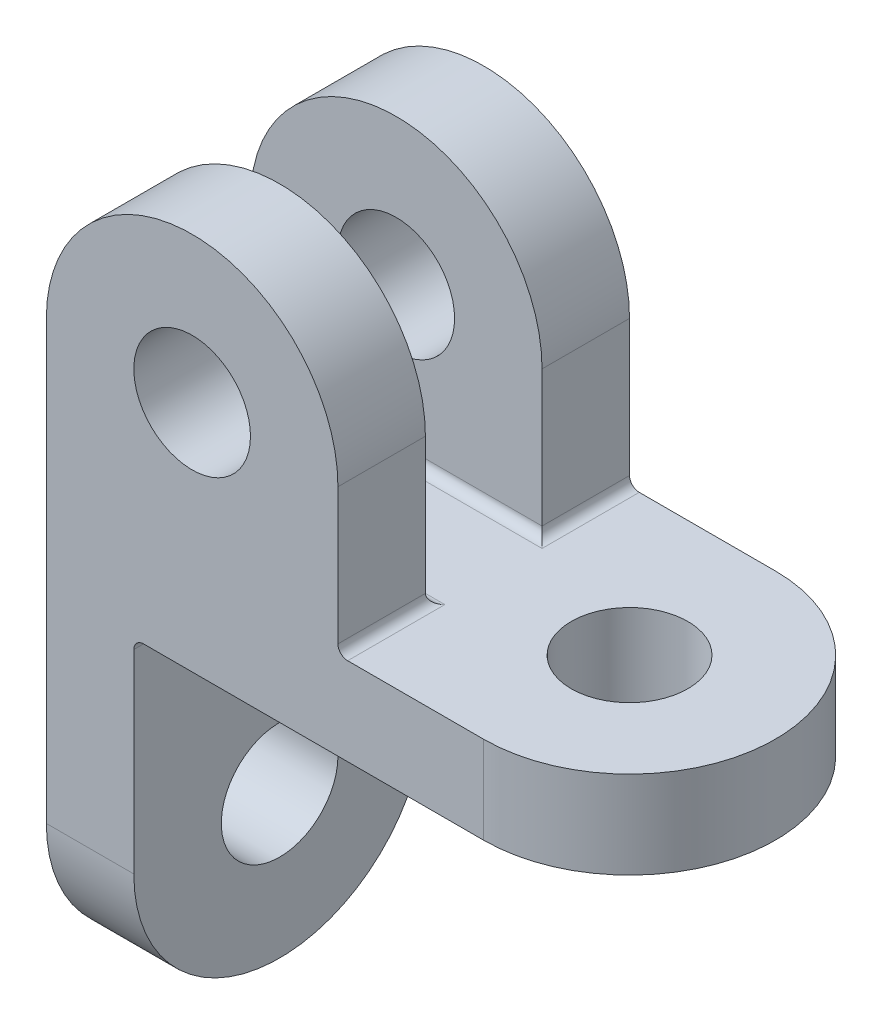
SolidWorks part; units mm, degrees
ref_plane "Front Plane" through (0, 0, 0) normal (0, 0, 1) x (1, 0, 0)
ref_plane "Top Plane" through (0, 0, 0) normal (0, 1, 0) x (1, 0, 0)
ref_plane "Right Plane" through (0, 0, 0) normal (1, 0, 0) x (0, 0, -1)
sketch "Sketch1" plane through (0, 0, 0) normal (0, 0, 1) x (1, 0, 0)
  line L0 (0, 0) -> (0, 60)
  line L1 (30, 60) -> (30, 45)
  line L2 (0, 45) -> (60, 45)
  line L3 (60, 45) -> (60, 36)
  line L4 (60, 36) -> (9, 36)
  line L5 (9, 36) -> (9, 0)
  line L6 (9, 0) -> (0, 0)
  arc A0 (0, 60) -> (30, 60) centre (15, 60) cw
  circle A1 centre (15, 60) radius 6
  dimension "D1" = 60
  dimension "D2" = 15
  dimension "D7" = 12
  dimension "D3" = 15
  dimension "D4" = 30
  dimension "D5" = 9
  dimension "D6" = 9
  dimension "D8" = 60
extrude "Boss-Extrude1" add sketch "Sketch1" along normal mid plane 30 contours L6 L5 L4 L3 L2 L0 region at (0.75, 22.5, 0)
extrude "Boss-Extrude2" add sketch "Sketch1<3>" along normal blind 9 from offset 6 contours A0 L0 L2 L1 A1 region at (0.4243, 52.5, 0)
sketch "Sketch1<3>" plane through (0, 0, 0) normal (0, 0, 1) x (1, 0, 0) same geometry as "Sketch1"
extrude "Boss-Extrude3" add sketch "Sketch1<4>" against normal blind 9 from offset 6 contours A0 L0 L2 L1 A1 region at (0.4243, 52.5, 0) offset against normal yes
sketch "Sketch1<4>" plane through (0, 0, 0) normal (0, 0, 1) x (1, 0, 0) same geometry as "Sketch1"
fillet "Fillet1" 2 edges at (60, 40.5, 15) (60, 40.5, -15) type full round first side face at (24.75, 37.125, 15) second side face at (24.75, 37.125, -15) middle face at (60, 40.5, 0)
fillet "Fillet2" 2 edges at (4.5, 0, 15) (4.5, 0, -15) type full round first side face at (21, 37.125, 15) second side face at (21, 37.125, -15) middle face at (4.5, 0, 0)
hole_wizard "Ø12.0mm Dowel Hole1" positions "3DSketch1" profile "Sketch4" hole size "Ø12.0" standard "AS"
sketch3d "3DSketch1"
  line L0 (45, 45, 0) -> (45, 36, 0) construction
  line L1 (9, 15, 0) -> (0, 15, 0) construction
  point P0 (45, 45, 0)
  point P4 (9, 15, 0)
sketch "Sketch4" plane through (45, 45, 0) normal (1, 0, 0) x (0, 0, 1)
  line L0 (0, 0) -> (0, 13)
  line L1 (0, 13) -> (6, 13)
  line L2 (6, 13) -> (6, 0)
  line L5 (6, 0) -> (0, 0)
  line L10 (0, 13) -> (-6, 13) construction
  line L11 (0, -6.35) -> (0, 107.95) construction
  dimension "Hole Dia." = 12
  dimension "Hole Depth" = 13
  dimension "Drill Angle" = 180
fillet "Fillet6" radius 1 1 edges at (9, 36, 0)
fillet "Fillet4" radius 1 1 edges at (30, 45, -10.5)
fillet "Fillet5" radius 1 1 edges at (30, 45, 10.5)
fillet "Fillet7" radius 1 2 edges at (15.5, 45, -6) (15.5, 45, 6)
